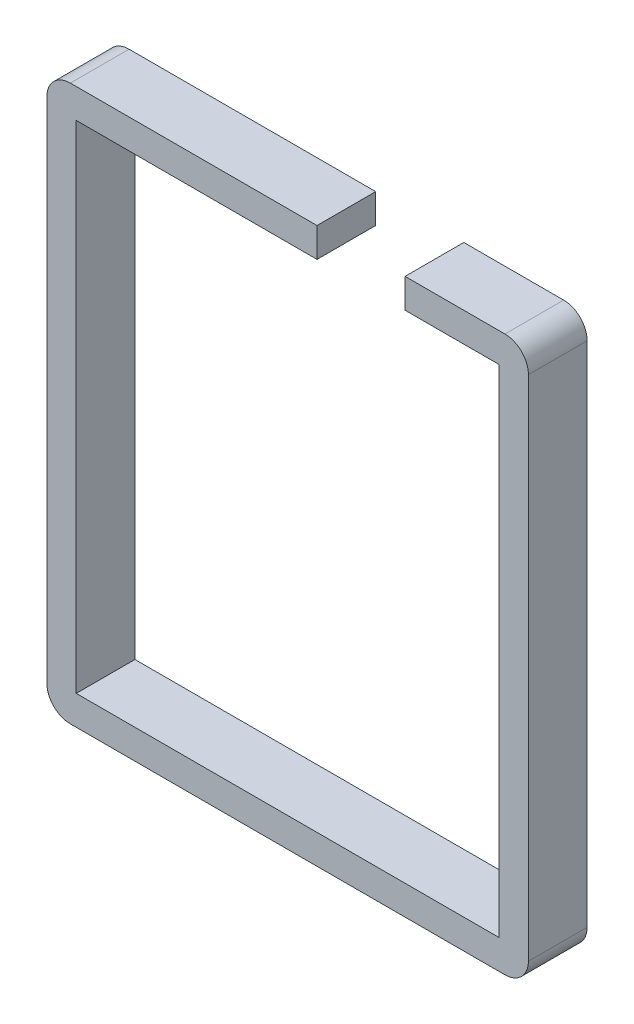
SolidWorks part; units mm, degrees
ref_plane "Plan de face" through (0, 0, 0) normal (0, 0, 1) x (1, 0, 0)
ref_plane "Plan de dessus" through (0, 0, 0) normal (0, 1, 0) x (1, 0, 0)
ref_plane "Plan de droite" through (0, 0, 0) normal (1, 0, 0) x (0, 0, -1)
sketch "Esquisse1" plane through (0, 0, 0) normal (0, 0, 1) x (1, 0, 0)
  line L1 (0, 0) -> (5, 0)
  line L2 (0, 0) -> (0, 89.5)
  line L4 (5, 5) -> (5, 89.5)
  line L16 (0, 0) -> (0, -5)
  line L21 (77, 94.5) -> (82, 94.5)
  line L22 (77, 89.5) -> (77, 5)
  line L24 (82, 94.5) -> (82, 5)
  line L29 (77, 94.5) -> (61, 94.5)
  line L33 (61, 89.5) -> (77, 89.5)
  line L34 (0, 94.5) -> (0, 89.5)
  line L37 (61, 94.5) -> (61, 89.5)
  line L42 (82, 0) -> (5, 0)
  line L43 (82, 0) -> (82, 5)
  line L44 (77, 5) -> (5, 5)
  line L46 (0, 94.5) -> (46, 94.5)
  line L47 (46, 94.5) -> (46, 89.5)
  line L48 (46, 89.5) -> (5, 89.5)
  dimension "D1" = 5
  dimension "D2" = 89.5
  dimension "D3" = 5
  dimension "D4" = 77
  dimension "D5" = 5
  dimension "D6" = 89.5
  dimension "D7" = 46
extrude "Boss.-Extru.1" add sketch "Esquisse1" along normal blind 10 contours L34 | L1 L4 L2 | L4 | L24 L21 L22 | L1 L42 L43 L24 L21 L29 L37 L33 L22 L44 L4 L48 L47 L46 L34 L2 region at (1.2512, 44.75, 0)
fillet "Congé3" radius 4 4 edges at (0, 0, 5) (82, 0, 5) (82, 94.5, 5) (0, 94.5, 5)
fillet "Congé2" radius 4 rebuild error yes
